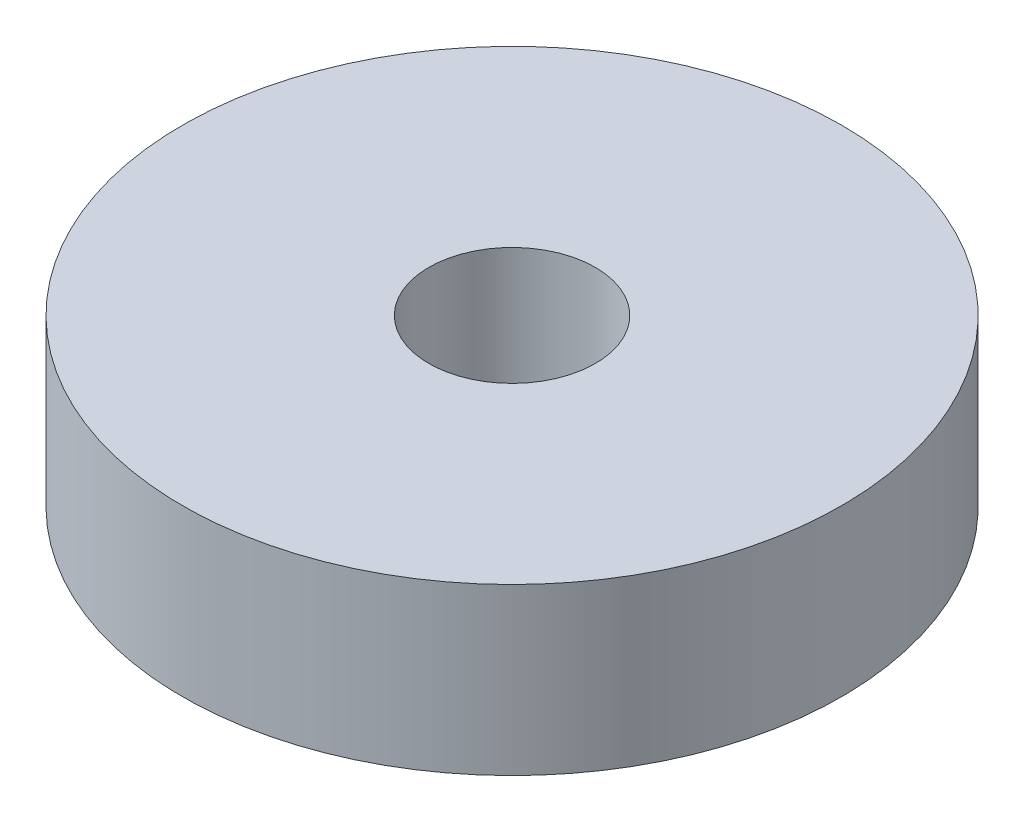
SolidWorks part; units mm, degrees
ref_plane "Front Plane" through (0, 0, 0) normal (0, 0, 1) x (1, 0, 0)
ref_plane "Top Plane" through (0, 0, 0) normal (0, 1, 0) x (1, 0, 0)
ref_plane "Right Plane" through (0, 0, 0) normal (1, 0, 0) x (0, 0, -1)
sketch "Gear Sketch" plane through (0, 0, 0) normal (0, 0, 1) x (1, 0, 0)
  line L0 (0, -100) -> (0, 200) construction
  line L1 (3.02, 58.5) -> (11.95, 58.5)
  line L2 (11.95, 58.5) -> (11.95, 64.5)
  line L3 (11.95, 64.5) -> (3.02, 64.5)
  line L4 (3.02, 64.5) -> (3.02, 58.5)
revolve "Gear" add sketch "Gear Sketch" angle 360 about L0
ref_axis "Engine Axis" through (13.145, 0, 0) along (-1, 0, 0)
